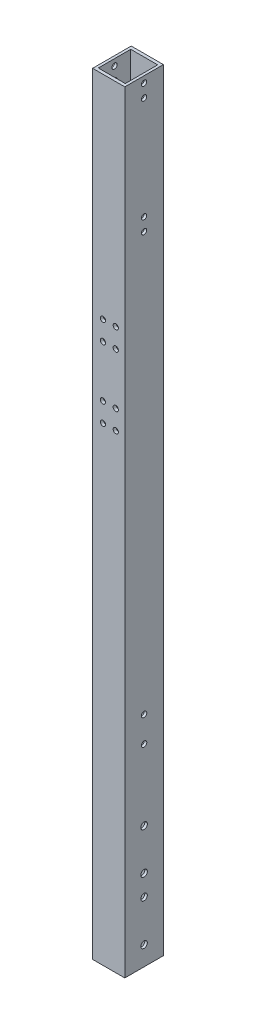
SolidWorks part; units mm, degrees
material "6061 合金"
ref_plane "前视基准面" through (0, 0, 0) normal (0, 0, 1) x (1, 0, 0)
ref_plane "上视基准面" through (0, 0, 0) normal (0, 1, 0) x (1, 0, 0)
ref_plane "右视基准面" through (0, 0, 0) normal (1, 0, 0) x (0, 0, -1)
sketch "草图1" plane through (0, 0, 0) normal (0, 1, 0) x (1, 0, 0)
  line L5 (-12.5, 15) -> (12.5, 15)
  line L6 (-12.5, 15) -> (-12.5, -15)
  line L11 (-12.5, -15) -> (12.5, -15)
  line L12 (12.5, 15) -> (12.5, -15)
  line L13 (-12.5, 15) -> (12.5, -15) construction
  line L14 (-12.5, -15) -> (12.5, 15) construction
  line L15 (-10.5, 12.6) -> (10.5, 12.6)
  line L16 (-10.5, 12.6) -> (-10.5, -12.6)
  line L17 (-10.5, -12.6) -> (10.5, -12.6)
  line L18 (10.5, 12.6) -> (10.5, -12.6)
  line L19 (-10.5, 12.6) -> (10.5, -12.6) construction
  line L20 (-10.5, -12.6) -> (10.5, 12.6) construction
  point P0 (0, 0)
  point P6 (0, 0)
  dimension "D2" = 2
  dimension "D3" = 30
  dimension "2" = 25
extrude "凸台-拉伸1" add sketch "草图1" along normal blind 600
sketch "草图3" plane through (-12.5, 0, 0) normal (-1, 0, 0) x (0, 0, 1)
  line L0 (-15, 600) -> (15, 600) construction
  line L1 (-15, 0) -> (15, 0) construction
  line L2 (0, 600) -> (0, 561.696) construction
  circle A0 centre (0, 595) radius 2.05
  circle A1 centre (0, 585) radius 2.05
  circle A2 centre (0, 505) radius 2.05
  circle A3 centre (0, 495) radius 2.05
  circle A4 centre (0, 15) radius 2.55
  circle A5 centre (0, 47) radius 2.55
  dimension "D1" = 4.1
  dimension "D5" = 5.1
  dimension "D8" = 80
  dimension "D2" = 10
  dimension "D3" = 5
  dimension "D6" = 32
  dimension "D7" = 15
  dimension "D4" = 2
extrude "切除-拉伸2" cut sketch "草图3" against normal through all
sketch "草图4" plane through (0, 0, 15) normal (0, 0, 1) x (1, 0, 0)
  line L1 (12.5, 600) -> (-12.5, 600) construction
  line L2 (-12.5, 400) -> (2.4514, 400) construction
  line L3 (-12.5, 600) -> (-12.5, 0) construction
  line L4 (-12.5, 600) -> (-12.5, 0) construction
  circle A0 centre (5.5, 435) radius 2.05
  circle A1 centre (-4.5, 435) radius 2.05
  circle A2 centre (-4.5, 420) radius 2.05
  circle A3 centre (5.5, 420) radius 2.05
  circle A4 centre (-4.5, 380) radius 2.05
  circle A5 centre (-4.5, 365) radius 2.05
  circle A6 centre (5.5, 365) radius 2.05
  circle A7 centre (5.5, 380) radius 2.05
  dimension "D2" = 4.1
  dimension "D1" = 165
  dimension "D3" = 10
  dimension "D5" = 20
  dimension "D7" = 8
  dimension "D6" = 2
  dimension "D4" = 2
extrude "切除-拉伸3" cut sketch "草图4" against normal through all
sketch "草图6" plane through (-12.5, 0, 0) normal (-1, 0, 0) x (0, 0, 1)
  circle A0 centre (0, 63) radius 2.55
  circle A1 centre (0, 95) radius 2.55
  dimension "D1" = 5.1
  dimension "D2" = 5.1
extrude "切除-拉伸4" cut sketch "草图6" against normal blind 42
sketch "草图7" plane through (12.5, 0, 0) normal (1, 0, 0) x (0, 0, -1)
  circle A0 centre (0, 150) radius 2.1 construction
  circle A1 centre (0, 170) radius 2.1 construction
  circle A2 centre (0, 150) radius 2.1
  circle A3 centre (0, 170) radius 2.1
extrude "切除-拉伸5" cut sketch "草图7" against normal up to next
sketch "草图8" plane through (-12.5, 0, 0) normal (-1, 0, 0) x (0, 0, 1)
  line L0 (0, 175) -> (0, 145) construction
  line L1 (5, 175) -> (5, 145)
  line L2 (-5, 175) -> (-5, 145)
  line L4 (-15, 0) -> (15, 0)
  line L5 (15, 0) -> (15, 600)
  line L6 (15, 600) -> (-15, 600)
  line L7 (-15, 600) -> (-15, 0)
  line L8 (-15, 0) -> (15, 0)
  line L9 (15, 0) -> (15, 600)
  line L10 (15, 600) -> (-15, 600)
  line L11 (-15, 600) -> (-15, 0)
  circle A0 centre (0, 150) radius 2.1 construction
  arc A4 (5, 175) -> (-5, 175) centre (0, 175) ccw
  arc A5 (-5, 145) -> (5, 145) centre (0, 145) ccw
  point P13 (0, 160)
  dimension "D3" = 5
  dimension "D2" = 30
  dimension "D4" = 160
  dimension "D1" = 0
extrude "切除-拉伸8" cut sketch "草图8" against normal blind 5 flip side to cut
